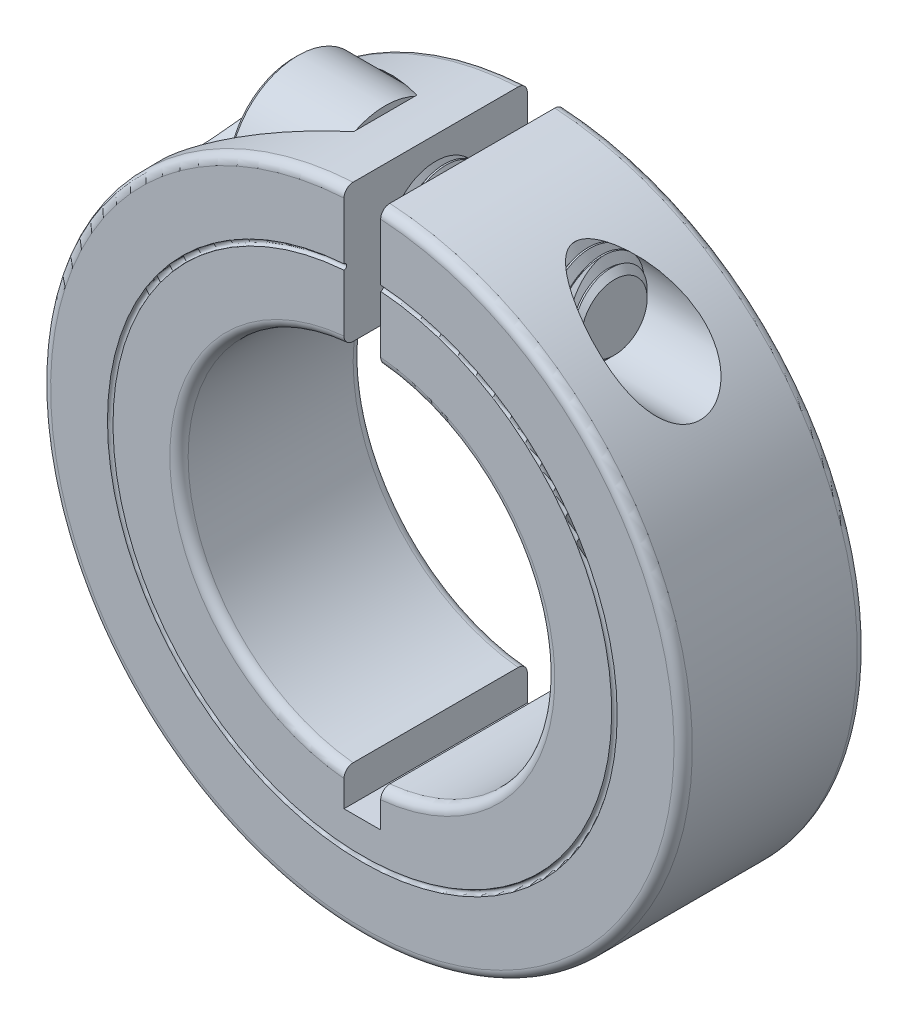
SolidWorks part; units mm, degrees
ref_plane "Front Plane" through (0, 0, 0) normal (0, 0, 1) x (1, 0, 0)
ref_plane "Top Plane" through (0, 0, 0) normal (0, 1, 0) x (1, 0, 0)
ref_plane "Right Plane" through (0, 0, 0) normal (1, 0, 0) x (0, 0, -1)
sketch "Sketch1" plane through (0, 0, 0) normal (0, 0, 1) x (1, 0, 0)
  line L0 (-1.27, 12.6363) -> (-1.27, 22.1887)
  line L2 (1.27, 12.6363) -> (1.27, 22.1887)
  line L3 (0, 0) -> (0, 12.6363) construction
  line L4 (1.27, 12.6363) -> (-1.27, 12.6363) construction
  line L5 (0, -22.225) -> (0, -12.7) construction
  line L6 (0, -12.7) -> (0, -17.4625) construction
  line L7 (-1.27, -12.6363) -> (-1.27, -15.0813)
  line L8 (-1.27, -15.0813) -> (1.27, -15.0813)
  line L9 (1.27, -12.6363) -> (1.27, -15.0813)
  line L10 (-1.27, 17.4125) -> (1.27, 17.4125) construction
  circle A0 centre (0, 0) radius 22.225 construction
  circle A1 centre (0, 0) radius 12.7 construction
  arc A3 (-1.27, 22.1887) -> (1.27, 22.1887) centre (0, 0) ccw
  arc A4 (1.27, -12.6363) -> (1.27, 12.6363) centre (0, 0) ccw
  arc A5 (-1.27, 12.6363) -> (-1.27, -12.6363) centre (0, 0) ccw
  point P4 (22.225, 0)
  point P5 (-22.225, 0)
  point P19 (0, -15.0812)
  dimension "Bore Dia" = 25.4
  dimension "OD" = 44.45
  dimension "Separation" = 2.54
extrude "Extrude1" add sketch "Sketch1" along normal mid plane 12.7
fillet "Fillet1" radius 0.635 6 edges at (0, -22.225, -6.35) (0, -22.225, 6.35) (-12.7, 0, 6.35) (-12.7, 0, -6.35) (12.7, 0, 6.35) (12.7, 0, -6.35)
sketch "Sketch2" plane through (0, 0, 0) normal (0, 1, 0) x (1, 0, 0)
  line L0 (0, 0) -> (-12.7, 0) construction
  line L1 (-12.7, 0) -> (-22.225, 0) construction
  line L2 (-17.4625, 6.35) -> (-17.4625, -6.35) construction
  line L3 (21.59, 6.35) -> (-21.59, 6.35) construction
  line L4 (-21.59, -6.35) -> (21.59, -6.35) construction
  line L5 (-22.225, 5.715) -> (-22.225, -5.715) construction
  line L6 (-12.7, 5.715) -> (-12.7, -5.715) construction
  line L8 (-17.653, -6.35) -> (-17.272, -6.35)
  line L9 (0, 6.35) -> (0, -6.35) construction
  line L10 (-1.27, 6.35) -> (-13.335, 6.35) construction
  arc A1 (-17.272, -6.35) -> (-17.653, -6.35) centre (-17.4625, -6.35) ccw
  point P1 (-17.4625, 0)
  dimension "D2" = 0.1905
revolve "Cut-Revolve1" cut sketch "Sketch2" angle 360 about L9
sketch "Sketch3" plane through (0, 0, 0) normal (0, 0, 1) x (1, 0, 0)
  line L0 (22.225, 17.4125) -> (-22.225, 17.4125)
  line L1 (-22.225, 17.4125) -> (-22.225, 12.5865)
  line L2 (-22.225, 12.5865) -> (-4.7625, 12.5865)
  line L4 (-4.7625, 12.5865) -> (-4.7625, 14.2375)
  line L7 (-4.7625, 14.2375) -> (22.225, 14.2375)
  line L8 (22.225, 14.2375) -> (22.225, 17.4125)
  line L9 (-22.225, 17.4125) -> (-27.051, 17.4125) construction
  line L10 (-1.27, 17.4125) -> (1.27, 17.4125) construction
  dimension "D2" = 4.7625
  dimension "D4" = 9.652
  dimension "Screw Dia" = 6.35
revolve "Cut-Revolve2" cut sketch "Sketch3" angle 360 about L9
sketch "Sketch4" plane through (0, 0, 0) normal (0, 0, 1) x (1, 0, 0)
  line L0 (-11.1125, 17.4125) -> (-11.1125, 22.175)
  line L2 (-11.1125, 22.175) -> (-4.7625, 22.175)
  line L3 (-4.7625, 22.175) -> (-4.7625, 20.5875)
  line L4 (-4.7625, 20.5875) -> (11.1125, 20.5875)
  line L5 (-4.7625, 12.5865) -> (-4.7625, 14.2375) construction
  line L6 (11.1125, 20.5875) -> (11.1125, 17.4125)
  line L7 (-4.7625, 14.2375) -> (22.225, 14.2375) construction
  line L8 (11.1125, 17.4125) -> (-11.1125, 17.4125)
  line L9 (11.1125, 20.5875) -> (11.1125, 14.2375) construction
  line L10 (-11.1125, 17.4125) -> (-15.875, 17.4125) construction
  line L11 (-22.225, 17.4125) -> (-27.051, 17.4125) construction
  dimension "Head Ht" = 6.35
  dimension "Screw Lg" = 15.875
  dimension "Head Dia" = 9.525
revolve "Revolve1" add sketch "Sketch4" angle 360 about L8
sketch "Sketch5" plane through (-11.1125, 0, 0) normal (-1, 0, 0) x (0, -1, 0)
  line L1 (-16.0377, -2.3812) -> (-14.6629, 0)
  line L2 (-14.6629, 0) -> (-16.0377, 2.3812)
  line L3 (-16.0377, 2.3812) -> (-18.7873, 2.3812)
  line L4 (-18.7873, 2.3812) -> (-20.1621, 0)
  line L5 (-20.1621, 0) -> (-18.7873, -2.3812)
  line L6 (-18.7873, -2.3812) -> (-16.0377, -2.3812)
  circle A0 centre (-17.4125, 0) radius 2.3812 construction
  dimension "Hex" = 4.7625
extrude "Cut-Extrude1" cut sketch "Sketch5" against normal blind 4.7625
chamfer "Chamfer1" distance 0.3175 angle 45 1 edges at (-11.1125, 22.175, 0)
sketch "Sketch6" plane through (11.1125, 0, 0) normal (1, 0, 0) x (0, 1, 0)
  circle A0 centre (17.4125, 0) radius 3.175 construction
  circle A1 centre (17.4125, 0) radius 3.175
  point P3 (20.5875, 0)
curve "Helix/Spiral1" pitch 0.9071 height 15.875 turns 17.5 parameters "Height"=15.875, "Pitch"=0.9071
sketch "Sketch7" plane through (0, 0, 0) normal (0, 0, 1) x (1, 0, 0)
  line L0 (11.5094, 19.9001) -> (11.0558, 20.6857) construction
  line L1 (11.0558, 20.6857) -> (11.9629, 20.6857) construction
  line L2 (11.9629, 20.6857) -> (11.5094, 19.9001) construction
  line L3 (11.1125, 20.5875) -> (11.9062, 20.5875) construction
  line L4 (11.4527, 19.9983) -> (11.5661, 19.9983)
  line L5 (11.5094, 20.6857) -> (11.5094, 20.5875) construction
  line L6 (11.5094, 19.9983) -> (11.5094, 19.9001) construction
  line L7 (11.4527, 19.9983) -> (11.0842, 20.6366)
  line L8 (11.0842, 20.6366) -> (11.9346, 20.6366)
  line L9 (11.9346, 20.6366) -> (11.5661, 19.9983)
  point P10 (11.5094, 20.6366)
  dimension "D1" = 0.9071
  dimension "D2" = 0.1134
chamfer "Chamfer2" distance 0.9071 angle 45 1 edges at (11.1125, 20.5875, 0)
sweep "Cut-Sweep1" cut profiles "Sketch7" path "Helix/Spiral1"
equation "\"D1@Sketch3\" = \"Screw Dia@Sketch3\""
equation "\"D1@Cut-Extrude1\" = \"Hex@Sketch5\""
equation "\"D1@Fillet1\" = \"Width@Extrude1\"*.05"
equation "\"D4@Sketch3\" = \"Head Dia@Sketch4\" + .005"
equation "\"Height@Helix/Spiral1\" = \"Screw Lg@Sketch4\""
equation "\"D1@Sketch7\" = \"Pitch@Helix/Spiral1\""
equation "\"D2@Sketch7\" = \"D1@Sketch7\"/8"
equation "\"D1@Chamfer2\" = \"Pitch@Helix/Spiral1\""
equation "\"Separation@Sketch1\" = \"Bore Dia@Sketch1\"/10"
equation "\"D2@Sketch3\" = \"Screw Dia@Sketch3\"*.750"
